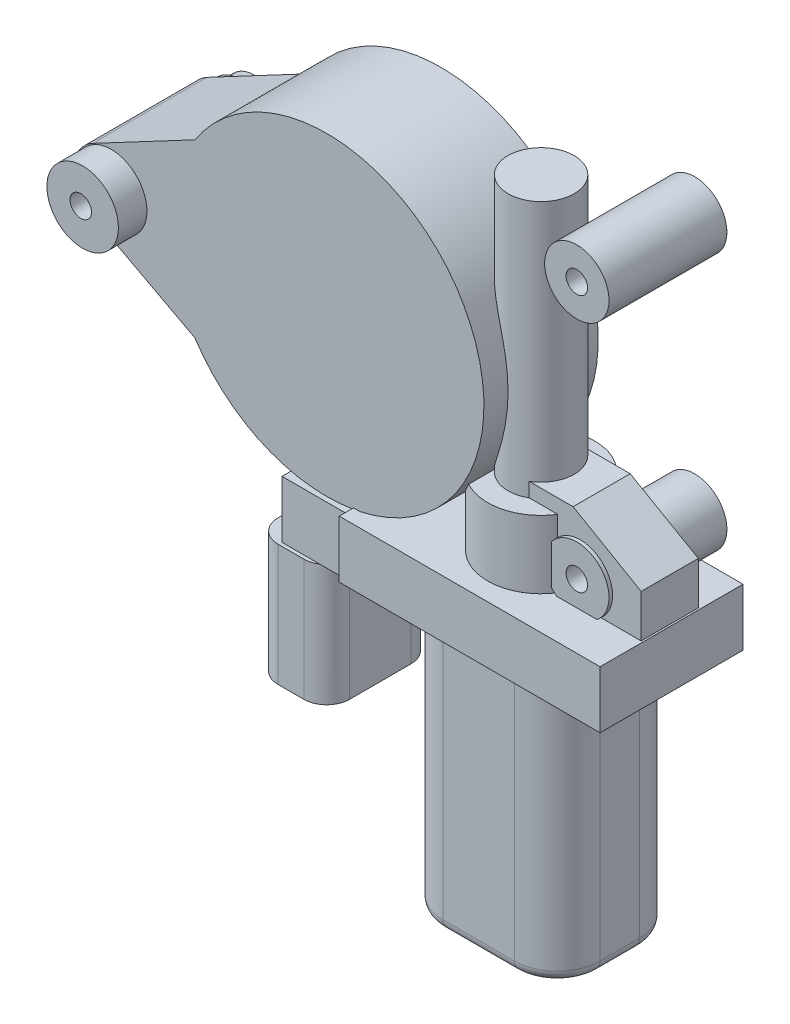
SolidWorks part; units mm, degrees
ref_plane "Front Plane" through (0, 0, 0) normal (0, 0, 1) x (1, 0, 0)
ref_plane "Top Plane" through (0, 0, 0) normal (0, 1, 0) x (1, 0, 0)
ref_plane "Right Plane" through (0, 0, 0) normal (1, 0, 0) x (0, 0, -1)
sketch "Sketch1" plane through (0, 0, 0) normal (0, 0, 1) x (1, 0, 0)
  line L0 (0, 0) -> (-48.26, 0) construction
  line L1 (-29.2721, 19.05) -> (-51.9778, 7.013)
  line L2 (-29.2721, -19.05) -> (-51.9778, -7.013)
  arc A0 (-29.2721, -19.05) -> (-29.2721, 19.05) centre (0, 0) ccw
  arc A1 (-51.9778, 7.013) -> (-51.9778, -7.013) centre (-48.26, 0) ccw
  point P9 (-51.9778, 7.013)
  point P10 (-51.9778, -7.013)
  dimension "D1" = 69.85
  dimension "D3" = 15.875
  dimension "D2" = 38.1
  dimension "D4" = 48.26
extrude "Boss-Extrude1" add sketch "Sketch1" along normal mid plane 25.4
sketch "Sketch2" plane through (0, 0, 12.7) normal (0, 0, 1) x (1, 0, 0)
  circle A0 centre (-47.8533, 0) radius 7.9375
extrude "Boss-Extrude2" add sketch "Sketch2" along normal blind 6.35
sketch "Sketch3" plane through (0, 0, 0) normal (0, 1, 0) x (1, 0, 0)
  line L0 (34.925, -12.7) -> (34.925, 12.7) construction
  circle A0 centre (34.925, 0) radius 7.3422
extrude "Boss-Extrude3" add sketch "Sketch3" along normal blind 38.1 and the other way blind 19.05
sketch "Sketch7" plane through (0, 0, -12.7) normal (0, 0, -1) x (-1, 0, 0)
  circle A0 centre (47.8533, 0) radius 7.9375 construction
  circle A1 centre (47.8533, 0) radius 7.1437
  dimension "D1" = 14.2875
extrude "Boss-Extrude6" add sketch "Sketch7" along normal blind 6.35
sketch "Sketch8" plane through (0, 0, -19.05) normal (0, 0, -1) x (-1, 0, 0)
  circle A0 centre (47.8533, 0) radius 6.35
  circle A1 centre (47.8533, 0) radius 7.1437
  dimension "D1" = 12.7
extrude "Cut-Extrude1" cut sketch "Sketch8" against normal blind 3.175
sketch "Sketch9" plane through (0, 0, 19.05) normal (0, 0, 1) x (1, 0, 0)
  circle A0 centre (-48.26, 0) radius 2.3812
  dimension "D1" = 4.7625
extrude "Cut-Extrude2" cut sketch "Sketch9" against normal through all
sketch "Sketch10" plane through (0, 0, 0) normal (0, 0, 1) x (1, 0, 0)
  line L1 (0, 0) -> (84.0882, 0) construction
  line L2 (50, 21.4312) -> (50, -21.4312) construction
  circle A0 centre (50, 28.575) radius 7.1437
  circle A1 centre (50, -28.575) radius 7.1437
  dimension "D1" = 14.2875
  dimension "D3" = 50
  dimension "D2" = 57.15
extrude "Boss-Extrude7" add sketch "Sketch10" along normal blind 7.1437 and the other way blind 19.05 separate body
sketch "Sketch12" plane through (0, 0, 0) normal (0, 0, 1) x (1, 0, 0)
  line L0 (63.4938, -24.6062) -> (63.4938, -46.8312)
  line L1 (63.4938, -24.6062) -> (48.3708, -15.875)
  line L2 (34.925, 38.1) -> (34.925, -42.8809) construction
  line L3 (42.2672, 38.1) -> (27.5828, 38.1) construction
  line L4 (48.3708, -15.875) -> (34.925, -15.875)
  line L5 (34.925, -15.875) -> (34.925, -46.8312)
  line L6 (34.925, -46.8312) -> (63.4938, -46.8312)
  line L7 (57.1438, -23.082) -> (57.1438, -34.95) construction
  circle A0 centre (50, -28.575) radius 7.1437 construction
  point P4 (57.1438, -28.575)
  dimension "D1" = 6.35
  dimension "D2" = 17.4625
  dimension "D3" = 60
  dimension "D4" = 22.225
  dimension "D5" = 3.9688
extrude "Boss-Extrude8" add sketch "Sketch12" along normal mid plane 12.7 contours L0 L6 L5 L4 L1
sketch "Sketch13" plane through (0, -19.05, 0) normal (0, -1, 0) x (1, 0, 0)
  line L0 (34.925, 6.35) -> (34.925, -6.35) construction
  line L1 (34.925, 6.35) -> (63.4938, 6.35) construction
  circle A0 centre (34.925, 0) radius 11.876
  point P4 (44.9608, 6.35)
  dimension "D1" = 6.35
extrude "Boss-Extrude9" add sketch "Sketch13" along normal up to surface (27.7812 mm away) up to face at (49.2094, -46.8312, 0)
sketch "Sketch11" plane through (0, 0, -19.05) normal (0, 0, -1) x (-1, 0, 0)
  circle A0 centre (-50, 28.575) radius 2.3812
  circle A1 centre (-50, -28.575) radius 2.3812
  dimension "D1" = 4.7625
  dimension "D2" = 4.7625
extrude "Cut-Extrude3" cut sketch "Sketch11" against normal through all
sketch "Sketch14" plane through (0, -46.8312, 0) normal (0, -1, 0) x (1, 0, 0)
  line L1 (5.9531, -15.875) -> (63.8969, -15.875)
  line L2 (5.9531, -15.875) -> (5.9531, 15.875)
  line L3 (5.9531, 15.875) -> (63.8969, 15.875)
  line L4 (63.8969, -15.875) -> (63.8969, 15.875)
  line L5 (5.9531, -15.875) -> (63.8969, 15.875) construction
  line L6 (5.9531, 15.875) -> (63.8969, -15.875) construction
  circle A0 centre (26.0592, -7.7929) radius 0.0721
  arc A1 (44.9608, 6.35) -> (44.9608, -6.35) centre (34.925, 0) ccw construction
  arc A2 (44.9608, 6.35) -> (44.9608, -6.35) centre (34.925, 0) ccw construction
  dimension "D1" = 31.75
  dimension "D2" = 57.9437
extrude "Boss-Extrude10" add sketch "Sketch14" against normal blind 12.7
sketch "Sketch15" plane through (0, -46.8312, 0) normal (0, -1, 0) x (1, 0, 0)
  line L0 (63.8969, 15.875) -> (5.9531, 15.875) construction
  line L1 (5.9531, 15.875) -> (5.9531, -15.875) construction
  line L2 (5.9531, -15.875) -> (63.8969, -15.875) construction
  line L3 (63.8969, -15.875) -> (63.8969, 15.875) construction
  line L4 (63.8969, 15.875) -> (5.9531, 15.875) construction
  line L5 (5.9531, 15.875) -> (5.9531, -15.875) construction
  line L6 (5.9531, -15.875) -> (63.8969, -15.875) construction
  line L7 (63.8969, -15.875) -> (63.8969, 15.875) construction
  line L8 (34.925, 15.875) -> (34.925, -15.875) construction
  line L9 (5.9531, 0) -> (63.8969, 0) construction
  line L11 (17.4625, -13.8906) -> (52.3875, -13.8906)
  line L12 (17.4625, -13.8906) -> (17.4625, 13.8906)
  line L13 (17.4625, 13.8906) -> (52.3875, 13.8906)
  line L14 (52.3875, -13.8906) -> (52.3875, 13.8906)
  line L15 (17.4625, -13.8906) -> (52.3875, 13.8906) construction
  line L16 (17.4625, 13.8906) -> (52.3875, -13.8906) construction
  point P8 (34.925, 0)
  dimension "D1" = 27.7812
  dimension "D2" = 34.925
extrude "Boss-Extrude11" add sketch "Sketch15" along normal blind 57.9437
fillet "Fillet1" radius 9.525 4 edges at (17.4625, -75.8031, 13.8906) (17.4625, -75.8031, -13.8906) (52.3875, -75.8031, -13.8906) (52.3875, -75.8031, 13.8906)
sketch "Sketch16" plane through (0, -104.775, 0) normal (0, -1, 0) x (1, 0, 0)
  line L0 (42.8625, 13.8906) -> (26.9875, 13.8906) construction
  line L1 (26.9875, -13.8906) -> (42.8625, -13.8906) construction
  line L2 (42.8625, 13.8906) -> (26.9875, 13.8906) construction
  line L3 (26.9875, -13.8906) -> (42.8625, -13.8906) construction
  line L4 (34.925, 13.8906) -> (34.925, -13.8906) construction
  circle A0 centre (34.925, 0) radius 4.7625
  dimension "D1" = 9.525
extrude "Boss-Extrude12" add sketch "Sketch16" along normal blind 7.9375
fillet "Fillet2" radius 1.5875 1 edges at (34.925, -112.7125, -4.7625)
sketch "Sketch17" plane through (5.9531, 0, 0) normal (-1, 0, 0) x (0, 0, 1)
  line L0 (-15.875, -34.1313) -> (-15.875, -46.8312) construction
  line L1 (15.875, -34.1313) -> (15.875, -46.8312) construction
  line L2 (-15.875, -34.1313) -> (-15.875, -46.8312) construction
  line L3 (15.875, -34.1313) -> (15.875, -46.8312) construction
  line L4 (-15.875, -40.4812) -> (15.875, -40.4812) construction
  line L5 (0, -40.4812) -> (0, -43.9389) construction
  line L7 (-11.1125, -50.2889) -> (11.1125, -50.2889)
  line L8 (-11.1125, -50.2889) -> (-11.1125, -37.5889)
  line L9 (-11.1125, -37.5889) -> (11.1125, -37.5889)
  line L10 (11.1125, -50.2889) -> (11.1125, -37.5889)
  line L11 (-11.1125, -50.2889) -> (11.1125, -37.5889) construction
  line L12 (-11.1125, -37.5889) -> (11.1125, -50.2889) construction
  line L13 (-12.7, -34.4139) -> (12.7, -34.4139) construction
  dimension "D1" = 22.225
  dimension "D2" = 12.7
  dimension "D3" = 3.175
extrude "Boss-Extrude13" add sketch "Sketch17" along normal blind 17.4625
sketch "Sketch18" plane through (0, -50.2889, 0) normal (0, -1, 0) x (1, 0, 0)
  line L0 (17.4625, 4.3656) -> (17.4625, -4.3656) construction
  line L1 (17.4625, 4.3656) -> (17.4625, -4.3656) construction
  line L2 (17.4625, 0) -> (-8.7312, 0) construction
  line L4 (-11.5887, -11.9063) -> (-5.8738, -11.9063)
  line L5 (-16.6687, -6.8262) -> (-16.6687, 6.8262)
  line L6 (-11.5887, 11.9062) -> (-5.8738, 11.9062)
  line L7 (-0.7937, -6.8262) -> (-0.7937, 6.8262)
  line L8 (-16.6687, -11.9063) -> (-0.7937, 11.9062) construction
  line L9 (-16.6687, 11.9062) -> (-0.7937, -11.9063) construction
  arc A0 (-5.8738, -11.9063) -> (-0.7937, -6.8262) centre (-5.8737, -6.8263) ccw
  arc A1 (-11.5887, -11.9063) -> (-16.6687, -6.8262) centre (-11.5887, -6.8263) cw
  arc A2 (-5.8738, 11.9062) -> (-0.7937, 6.8262) centre (-5.8737, 6.8262) cw
  arc A3 (-16.6687, 6.8262) -> (-11.5887, 11.9062) centre (-11.5887, 6.8262) cw
  dimension "D4" = 5.08
  dimension "D1" = 18.2562
  dimension "D2" = 15.875
  dimension "D3" = 23.8125
extrude "Boss-Extrude14" add sketch "Sketch18" along normal blind 26.9875
fillet "Fillet3" radius 2.54 8 edges at (20.2523, -104.775, -11.1008) (17.4625, -104.775, 0) (20.2523, -104.775, 11.1008) (34.925, -104.775, 13.8906) (49.5977, -104.775, 11.1008) (52.3875, -104.775, 0) (49.5977, -104.775, -11.1008) (34.925, -104.775, -13.8906)
sketch "Sketch19" plane through (0, 0, -12.7) normal (0, 0, -1) x (-1, 0, 0)
  circle A0 centre (0, 0) radius 3.9688
  dimension "D1" = 7.9375
extrude "Cut-Extrude4" cut sketch "Sketch19" against normal blind 2.54
